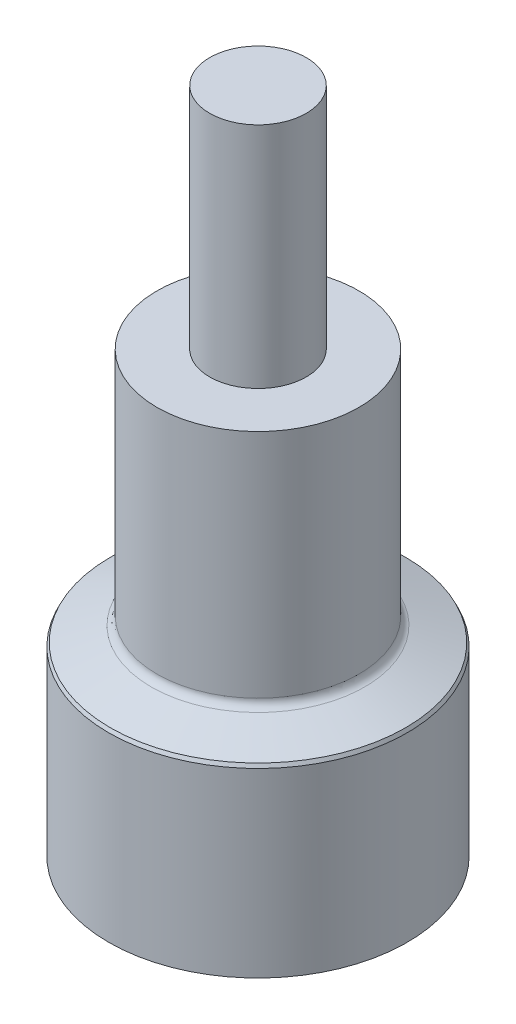
SolidWorks part; units mm, degrees
ref_plane "Спереди" through (0, 0, 0) normal (0, 0, 1) x (1, 0, 0)
ref_plane "Сверху" through (0, 0, 0) normal (0, 1, 0) x (1, 0, 0)
ref_plane "Справа" through (0, 0, 0) normal (1, 0, 0) x (0, 0, -1)
sketch "Эскиз2" plane through (0, 0, 0) normal (0, 0, 1) x (1, 0, 0)
  line L0 (0, 0) -> (-17, 0)
  line L1 (-17, 0) -> (-17, 21)
  line L2 (-17, 21) -> (-11.5, 23.0018)
  line L3 (-11.5, 23.0018) -> (-11.5, 50)
  line L4 (-11.5, 50) -> (-5.5, 50)
  line L5 (-5.5, 50) -> (-5.5, 76)
  line L6 (-5.5, 76) -> (0, 76)
  line L7 (0, 76) -> (0, 0)
  dimension "D1" = 76
  dimension "D2" = 17
  dimension "D3" = 5.5
  dimension "D4" = 11.5
  dimension "D5" = 21
  dimension "D6" = 26
  dimension "D7" = 70
revolve "Повернуть2" add sketch "Эскиз2" angle 360 about L7
chamfer "Фаска1" distance 0.2 angle 45 1 edges at (0, 21, 17) first distance on face at (0, 21, 17)
fillet "Скругление2" radius 1 1 edges at (0, 23.0018, 11.5)
sketch "Эскиз3" plane through (0, 0, 0) normal (0, 0, 1) x (1, 0, 0)
  line L0 (0, 0) -> (0, 76) construction
  line L1 (-24.5, 50) -> (24.5, 50)
  line L2 (24.5, 50) -> (24.5, 39)
  line L3 (24.5, 39) -> (-24.5, 39)
  line L4 (-24.5, 50) -> (-24.5, 39)
  point P7 (25.574, 45.3371)
  point P9 (0, 39)
  point P10 (0, 50)
  dimension "D1" = 76
  dimension "D2" = 26
  dimension "D3" = 11
  dimension "D4" = 24.5
